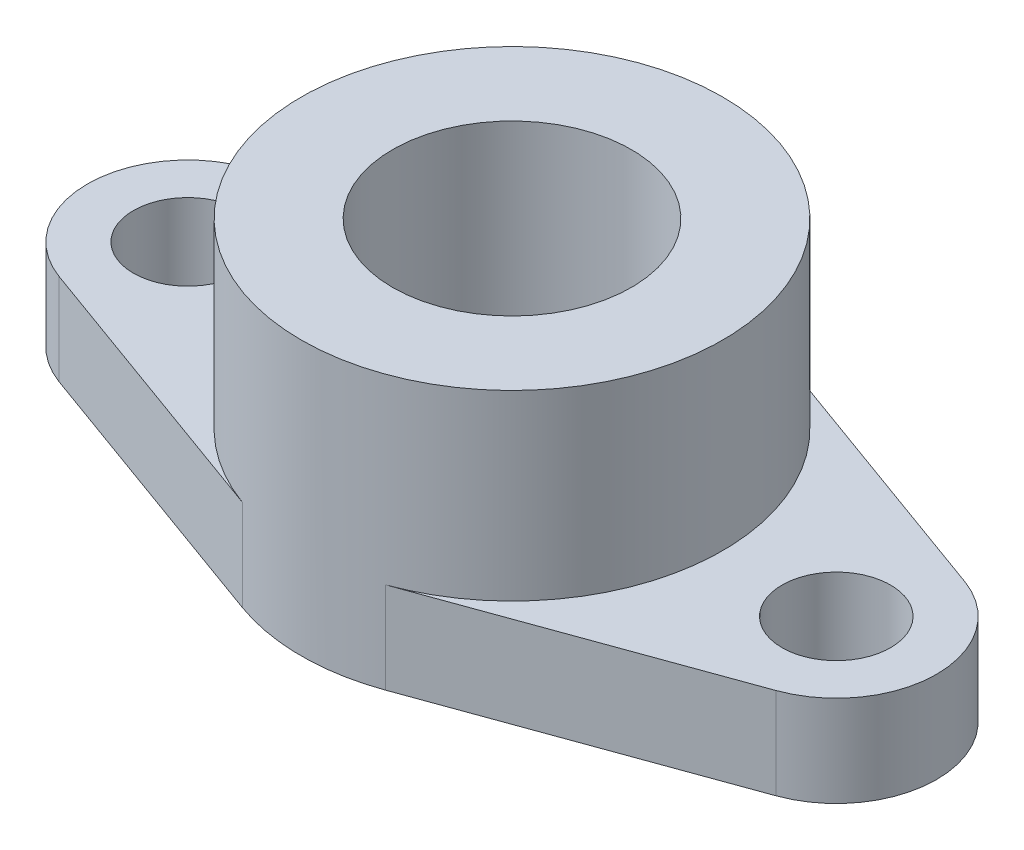
SolidWorks part; units mm, degrees
ref_plane "Front Plane" through (0, 0, 0) normal (0, 0, 1) x (1, 0, 0)
ref_plane "Top Plane" through (0, 0, 0) normal (0, 1, 0) x (1, 0, 0)
ref_plane "Right Plane" through (0, 0, 0) normal (1, 0, 0) x (0, 0, -1)
sketch "Sketch1" plane through (0, 0, 0) normal (0, 1, 0) x (1, 0, 0)
  line L0 (0, 0) -> (6.5484, 0) construction
  line L1 (0, 0) -> (17.78, 0) construction
  line L2 (19.651, 5.172) -> (3.9286, 10.8597)
  line L3 (3.9286, -10.8597) -> (19.651, -5.172)
  line L4 (0, 0) -> (-17.78, 0) construction
  line L5 (-19.651, 5.172) -> (-3.9286, 10.8597)
  line L6 (-19.651, -5.172) -> (-3.9286, -10.8597)
  circle A0 centre (0, 0) radius 4.826
  circle A1 centre (0, 0) radius 6.5484 construction
  arc A2 (3.9286, 10.8597) -> (3.9286, -10.8597) centre (0, 0) ccw construction
  circle A3 centre (17.78, 0) radius 2.9766
  arc A4 (19.651, -5.172) -> (19.651, 5.172) centre (17.78, 0) ccw
  circle A5 centre (0, 0) radius 11.5484 construction
  circle A6 centre (-17.78, 0) radius 2.9766
  arc A7 (-19.651, 5.172) -> (-19.651, -5.172) centre (-17.78, 0) ccw
  arc A10 (-3.9286, -10.8597) -> (3.9286, -10.8597) centre (0, 0) ccw
  arc A11 (3.9286, 10.8597) -> (-3.9286, 10.8597) centre (0, 0) ccw
  dimension "D1" = 9.652
  dimension "D2" = 13.0969
  dimension "D3" = 23.0969
  dimension "D5" = 5.9531
  dimension "D7" = 5.9531
  dimension "D6" = 5.5
  dimension "D4" = 17.78
  dimension "D8" = 17.78
extrude "Boss-Extrude1" add sketch "Sketch1" along normal blind 5
sketch "Sketch2" plane through (0, 5, 0) normal (0, 1, 0) x (1, 0, 0)
  circle A0 centre (0, 0) radius 11.5484
  arc A1 (-3.9286, -10.8597) -> (3.9286, -10.8597) centre (0, 0) ccw construction
  circle A2 centre (0, 0) radius 6.5484
  dimension "D1" = 13.0969
extrude "Boss-Extrude2" add sketch "Sketch2" along normal blind 10
equation "\"z\" = 8\t\t\t\t'number of blades"
equation "\"de\" = 0.43in\t\t\t'entrance eye diameter"
equation "\"de_length\" = 10mm\t\t'entrance eye consistent length"
equation "\"d_exit\" = 0.18in \t\t'throat aka d1"
equation "\"d2\" = 2.1in \t\t\t'outer diameter of the impeller"
equation "\"b2\" = .2in\t\t\t'tip height from disc surface at d2; slightly higher than d_exit"
equation "\"b1\" = \"b2\" + (\"d2\"/2 - \"de\"/2)*tan(\"theta\") \t\t\t'tip height from disc surface at inlet eye"
equation "\"theta\" = 12\t\t\t'angle of blades from inner to outer "
equation "\"ae\" = 3.14*(\"de\"^2)/4\t\t'entrance eye area'"
equation "\"ce\" = 3.14*\"de\"\t\t'entrance eye circumference"
equation "\"av_ratio\" = .325\t\t'ratio of av/ae at N_s of 470, range is .275 to .375, .325 ideal. High ratio means bigger area means smaller blades"
equation "\"av\" = \"ae\"*\"av_ratio\"\t\t'area between just two blades"
equation "\"s_open\" = \"av\"/\"b1\"\t\t'width of open area"
equation "\"s\"=\"ce\" - \"z\"*\"s_open\""
equation "\"min blade thickness\" = .15in"
equation "\"bearing OD\" = 30mm"
equation "\"bearing ID\"= 10mm"
equation "\"bearing depth\"= 9mm"
equation "\"bearing outer race thickness\"= 1mm"
equation "\"bearing inner race thickness\"= 1mm"
equation "\"bearing bore\" = \"bearing depth\" + 1mm"
equation "\"lower seal OD\" = .917in\t\t'this is https://www.mcmaster.com/#9281k121/=174001b"
equation "\"lower seal ID\"= .375in"
equation "\"lower seal depth\" = .625in + .218in"
equation "\"lower seal bore\" = \"lower seal depth\" + 1mm"
equation "\"upper seal OD\" = 1.125in\t'this is https://www.mcmaster.com/#5154t33/=173zuau, needs to be visually inspected before machining!"
equation "\"upper seal ID\"= 0.625in"
equation "\"upper seal depth\"= .25in\t'aka height; these values need to be confirmed by inspection!! We may want to compress the height."
equation "\"upper seal bore\" = \"upper seal depth\" + 1mm"
equation "\"big o-ring thickness\" = .139in"
equation "\"big o-ring OD\" = 2.734in"
equation "\"big o-ring ID\" = 3.012in"
equation "\"big o-ring groove depth\" = \"big o-ring thickness\"*4/5"
equation "\"impeller center height\" = \"impeller base thickness\" + \"b1\"\t'impeller height at de"
equation "\"impeller outer height\" = \"impeller base thickness\" + \"b2\"\t'impeller height at de"
equation "\"impeller upper clearance\"= .5mm"
equation "\"impeller horizontal clearance\"= (\"d2\"*1.15 - \"d2\")/2 \t\t'clearance based on D2-D3 ratio for circular volute, ranges 1.15 to 1.2"
equation "\"impeller bottom clearance\"= .5mm"
equation "\"impeller base thickness\"= 2mm"
equation "\"impeller dowel diameter\" = 2mm"
equation "\"impeller bolt head diameter\" = \"m4 head bore diameter\""
equation "\"impeller bolt head depth\" = 4mm"
equation "\"impeller bolt stop depth\" = 3mm"
equation "\"impeller bolt bore\" = \"m4 clearance\""
equation "\"impeller shaft bore depth\" = 12mm"
equation "\"impeller shaft bore\" = 8mm"
equation "\"impeller boss depth\" = \"impeller shaft bore depth\"+\"impeller bolt stop depth\"+\"impeller bolt head depth\"-\"impeller base thickness\""
equation "\"impeller boss diameter\" = \"upper seal ID\""
equation "\"impeller dowel length\" = 2mm*2 + \"impeller shaft bore\""
equation "\"coupler motor shaft hole ID\"= 8mm"
equation "\"coupler OD\"= 17mm"
equation "\"coupler length\"= 25mm"
equation "\"motor OD\" = 64mm"
equation "\"motor shaft diameter\"= 8mm"
equation "\"motor shaft pride\"= 32mm"
equation "\"motor to bearing plate distance\" = \"motor shaft pride\" + 2mm +\"coupler length\"/2"
equation "\"square plate bolt bore\" = \"m8 clearance\""
equation "\"square plate bolt head diameter\" = 13.5mm"
equation "\"square plate bolt head depth\" = 8mm"
equation "\"square plate bolt pattern diameter\"= 3.5in"
equation "\"motor mount center bore\"= \"coupler OD\"+ 4mm"
equation "\"motor mount post radius\"= ( 3 * \"square plate bolt bore\" ) / 2"
equation "\"motor mount m4 screw hole diameter\"= 4mm"
equation "\"motor mount m4 head diameter\"= 7.25mm"
equation "\"motor mount m4 head depth\"= 4mm"
equation "\"motor mount m4 pattern diamater\" = 30mm"
equation "\"motor mount plate thickness\"= 8mm + \"motor mount m4 head depth\""
equation "\"bearing plate stop ID\" = \"bearing OD\" - 4mm"
equation "\"bearing plate stop depth\" = 3mm"
equation "\"bearing plate thickness\" = \"bearing bore\" + \"bearing plate stop depth\" + \"shaft bearing stop length\""
equation "\"lower seal plate lip depth\" = 2mm"
equation "\"lower seal plate lip ID\" = \"lower seal OD\" - 3mm"
equation "\"lower seal plate thickness\" = \"lower seal plate lip depth\" + \"lower seal bore\""
equation "\"shaft coupler section diameter\" = 8mm"
equation "\"shaft coupler section length\" = \"motor to bearing plate distance\" - \"motor shaft pride\" - 2mm"
equation "\"shaft bearing section diameter\" = \"bearing ID\""
equation "\"shaft bearing section length\" = \"bearing plate stop depth\" + \"bearing depth\""
equation "\"shaft bearing stop diameter\" = \"bearing ID\" + 4mm"
equation "\"shaft bearing stop length\" = 3mm"
equation "\"shaft lower seal section diameter\" = \"lower seal ID\""
equation "\"shaft lower seal section length\" = \"lower seal plate thickness\" + 1mm"
equation "\"shaft impeller section diameter\" = \"impeller shaft bore\""
equation "\"shaft impeller section length\" = \"upper seal plate thickness\" + \"upper seal plate riser\" + \"impeller bottom clearance\" + \"impeller base thickness\" - \"impeller bolt head depth\" - \"impeller bolt stop depth\""
equation "\"upper seal plate thickness\" = \"upper seal plate pressure hole diameter\"+10mm"
equation "\"upper seal plate lip ID\" = \"upper seal OD\" - 3mm"
equation "\"upper seal plate riser\" = 6.59mm \t\t'this number needs to be read from the housing file"
equation "\"upper seal plate pressure hole diameter\" = .125in\t'this is 1/8 drill "
equation "\"upper seal plate pressure tap diameter\" = .328125in \t'this is 21/64 drill for a 1/8 ANPT tap"
equation "\"upper seal plate pressure tap grip\" = 5mm\t\t'this is the area around the tap so it doesn't crack"
equation "\"upper seal plate pressure tap depth\" = 12"
equation "\"impeller cavity center height\"= \"impeller bottom clearance\" + \"impeller upper clearance\" + \"impeller center height\""
equation "\"impeller cavity diameter\"= 2 * \"impeller horizontal clearance\" + \"d2\" \t\t\t\t\t\t\t\t\t'called D3 analytically"
equation "\"impeller cavity outer height\"= \"impeller bottom clearance\" + \"impeller upper clearance\" + \"impeller base thickness\" + \"b2\" \t\t'this is height at impeller diameter d2, not at d3"
equation "\"impeller housing thickness\"= \"impeller housing exit threaded diameter\" + 2*\"impeller housing outlet grip\""
equation "\"impeller housing diameter\" = \"square plate bolt pattern diameter\" + 2*\"motor mount post radius\""
equation "\"impeller housing bolt count\" = 8"
equation "\"impeller housing bolt diameter\" = \"m6 clearance\""
equation "\"impeller housing bolt pattern diameter\" = 3.5in"
equation "\"impeller housing threaded inlet diameter\" = 0.515625in \t'this is the 33/64 drill size for 9/16-18 fitting, expecting swagelok SS-8FK0-1-6STH fitting"
equation "\"impeller housing threaded inlet depth\"= 10mm"
equation "\"impeller housing exit threaded diameter\"= 0.515625in \t\t'this is the 33/64 drill size for 9/16-18 fitting, expecting swagelok SS-8FK0-1-6STH fitting"
equation "\"impeller housing exit threaded depth\"= 10mm"
equation "\"impeller housing diffuser conical angle\"=10"
equation "\"impeller housing diffuser tangent angle\"=5"
equation "\"impeller housing diffuser final diameter\" = .38in\t\t'aka d2'"
equation "\"impeller housing outlet grip\" = 5mm"
equation "\"end mill size\" = 0.375in\t'for 3/8 endmill"
equation "\"m4 clearance\" = 0.171875in \t'this is 11/64 bit for 4.36mm"
equation "\"m4 tap\" = 0.125in\t\t'this is 1/8 bit for 3.17mm"
equation "\"m4 head bore diameter\" = 7.5mm"
equation "\"m4 head bore depth\" = 5mm\t'actual is ~4mm"
equation "\"m6 clearance\" = 0.234375in\t'this is 15/64 bit = 5.95mm, could use 6mm bit, B bit for 6.04mm or 1/4 bit for 6.35mm"
equation "\"m6 tap\" = 5mm\t\t\t'5mm is appropriate, could use 13/64 or #5,6,7"
equation "\"m6 head bore diameter\" = 11mm\t\t"
equation "\"m6 head bore depth\" = 7mm\t'actual is 6mm"
equation "\"m8 clearance\" = 0.3125in\t'this is 5/16in for 7.93mm, could use 8mm, O,P, or 21/64"
equation "\"m8 tap\" = 0.265625in\t\t'this is 17/64 for 6.746875mm"
equation "\"m8 head bore diameter\" = 14mm"
equation "\"m8 head bore depth\" = 9mm\t'actual is 8mm"
equation "\"D1@Sketch1\"=\"impeller housing diffuser final diameter\""
equation "\"D2@Sketch1\"=\"impeller housing exit threaded diameter\""
equation "\"D3@Sketch1\"=\"impeller housing exit threaded diameter\"+\"impeller housing outlet grip\"*2 "
equation "\"D5@Sketch1\"=\"m6 clearance\""
equation "\"D7@Sketch1\"=\"m6 clearance\""
equation "\"D6@Sketch1\"=\"m6 head bore diameter\"/2"
equation "\"D1@Sketch2\"=\"impeller housing exit threaded diameter\""
equation "\"D1@Boss-Extrude2\"=10mm"
equation "\"diffuser cartridge OD\" =.75in"
equation "\"diffuser flange bolt pattern diameter\" = 1.4in"
equation "\"D4@Sketch1\"=\"diffuser flange bolt pattern diameter\"/2"
equation "\"D8@Sketch1\"=\"diffuser flange bolt pattern diameter\"/2"
